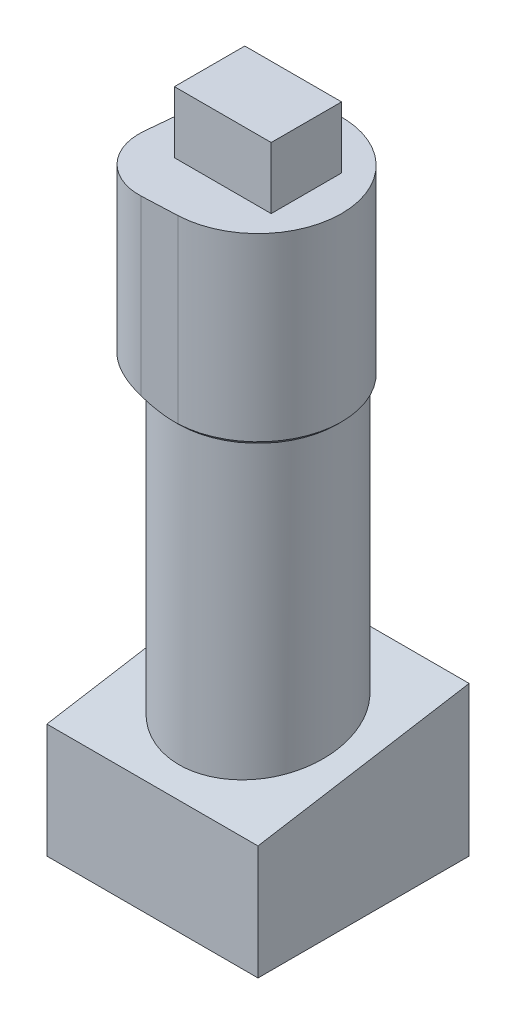
SolidWorks part; units mm, degrees
ref_plane "Front" through (0, 0, 0) normal (0, 0, 1) x (1, 0, 0)
ref_plane "Top" through (0, 0, 0) normal (0, 1, 0) x (1, 0, 0)
ref_plane "Right" through (0, 0, 0) normal (1, 0, 0) x (0, 0, -1)
sketch "Sketch1" plane through (0, 0, 0) normal (0, 1, 0) x (1, 0, 0)
  line L1 (-12, -12) -> (12, -12)
  line L2 (-12, -12) -> (-12, 12)
  line L3 (-12, 12) -> (12, 12)
  line L4 (12, -12) -> (12, 12)
  line L5 (-12, -12) -> (12, 12) construction
  line L6 (-12, 12) -> (12, -12) construction
  point P0 (0, 0)
  dimension "D1" = 24
extrude "Boss-Extrude1" add sketch "Sketch1" along normal blind 17
sketch "Sketch2" plane through (-12, 0, 0) normal (-1, 0, 0) x (0, 0, 1)
  line L0 (-12, 17) -> (12, 13)
  line L1 (12, 17) -> (12, 0) construction
  line L2 (12, 13) -> (12, 17)
  line L3 (12, 17) -> (-12, 17)
  dimension "D1" = 4
extrude "Cut-Extrude1" cut sketch "Sketch2" against normal through all
sketch "Sketch3" plane through (0, 0, 0) normal (0, -1, 0) x (1, 0, 0)
  circle A0 centre (0, 0) radius 9
  dimension "D1" = 18
extrude "Boss-Extrude2" add sketch "Sketch3" against normal blind 52
sketch "Sketch4" plane through (0, 52, 0) normal (0, 1, 0) x (1, 0, 0)
  line L0 (-9.4566, 0.9073) -> (-9.8408, -3.0977)
  line L1 (-3.6088, -9.6651) -> (0.4108, -9.4911)
  arc A0 (0.4108, -9.4911) -> (-9.4566, 0.9073) centre (0, 0) ccw
  arc A1 (-9.8408, -3.0977) -> (-3.6088, -9.6651) centre (-3.8683, -3.6707) ccw
  dimension "D1" = 9.5
  dimension "D2" = 6
extrude "Boss-Extrude3" add sketch "Sketch4" along normal blind 16
chamfer "Chamfer1" distance 5 angle 45 1 edges at (0, 52, -9)
sketch "Sketch5" plane through (0, 68, 0) normal (0, 1, 0) x (1, 0, 0)
  line L5 (-5.5, -4) -> (5.5, -4)
  line L6 (-5.5, -4) -> (-5.5, 4)
  line L7 (-5.5, 4) -> (5.5, 4)
  line L8 (5.5, -4) -> (5.5, 4)
  line L9 (-5.5, -4) -> (5.5, 4) construction
  line L10 (-5.5, 4) -> (5.5, -4) construction
  point P0 (0, 0)
  dimension "D1" = 8
  dimension "D2" = 11
extrude "Boss-Extrude4" add sketch "Sketch5" along normal blind 7
sketch "Sketch6" plane through (0, 0, -12) normal (0, 0, -1) x (-1, 0, 0)
  line L0 (-12, 17) -> (12, 17) construction
  circle A0 centre (5, 12) radius 2.05
  circle A2 centre (-5, 12) radius 2.05
  dimension "D1" = 4.1
  dimension "D2" = 4.1
  dimension "D3" = 5
  dimension "D4" = 5
  dimension "D5" = 5
extrude "Cut-Extrude2" cut sketch "Sketch6" against normal blind 6
